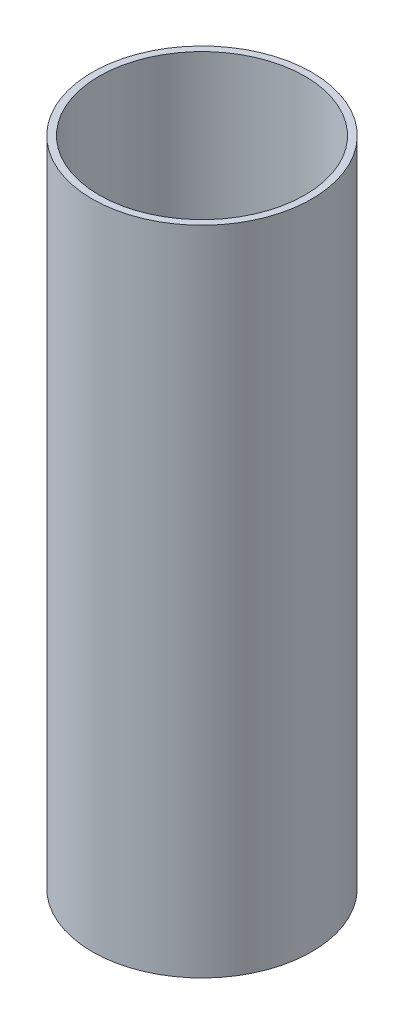
SolidWorks part; units mm, degrees
ref_plane "Спереди" through (0, 0, 0) normal (0, 0, 1) x (1, 0, 0)
ref_plane "Сверху" through (0, 0, 0) normal (0, 1, 0) x (1, 0, 0)
ref_plane "Справа" through (0, 0, 0) normal (1, 0, 0) x (0, 0, -1)
sketch "Sketch1" plane through (0, 0, 0) normal (0, 1, 0) x (1, 0, 0)
  circle A0 centre (0, 0) radius 16
  circle A1 centre (0, 0) radius 15
  dimension "D1" = 32
  dimension "D2" = 30
extrude "Boss-Extrude1" add sketch "Sketch1" along normal blind 85
sketch "Sketch4" plane through (0, 0, 0) normal (0, 1, 0) x (1, 0, 0)
  circle A0 centre (0, 0) radius 15
  circle A1 centre (0, 0) radius 16
  dimension "D1" = 30
  dimension "D2" = 32
extrude "Boss-Extrude2" add sketch "Sketch4" against normal blind 10
